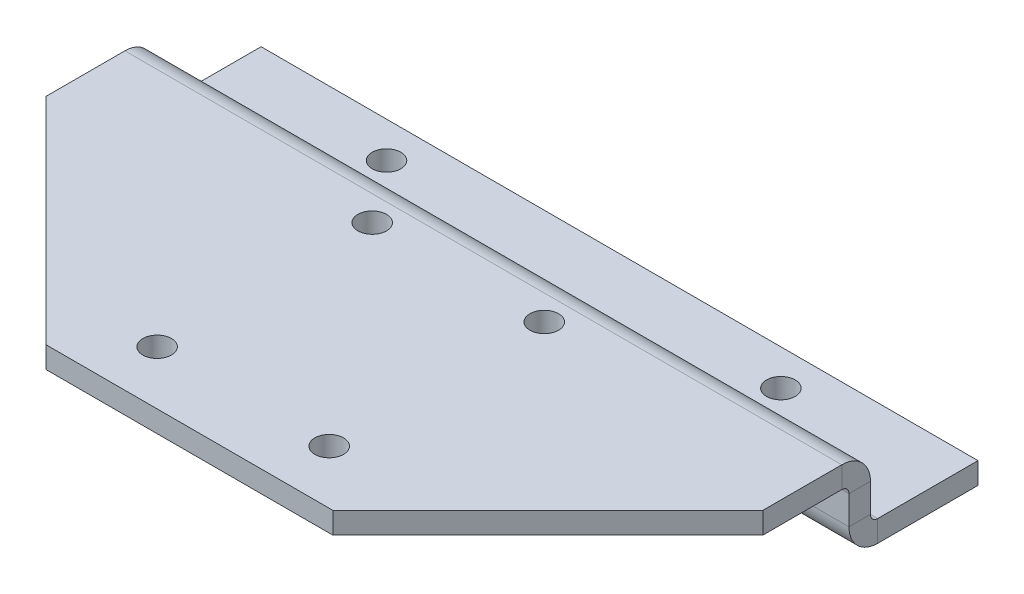
SolidWorks part; units mm, degrees
note: The reader was unsure of these and kept them because the rebuilt part matched: flange length of "Edge-Flange1", "Edge-Flange2".
material "6061 Alloy"
ref_plane "Front Plane" through (0, 0, 0) normal (0, 0, 1) x (1, 0, 0)
ref_plane "Top Plane" through (0, 0, 0) normal (0, 1, 0) x (1, 0, 0)
ref_plane "Right Plane" through (0, 0, 0) normal (1, 0, 0) x (0, 0, -1)
sketch "Sketch1" plane through (0, 0, 0) normal (0, 1, 0) x (1, 0, 0)
  line L1 (-50, 22.5) -> (50, 22.5)
  line L2 (-50, 22.5) -> (-50, -22.5)
  line L3 (-50, -22.5) -> (50, -22.5)
  line L4 (50, 22.5) -> (50, -22.5)
  line L5 (-50, 22.5) -> (50, -22.5) construction
  line L6 (-50, -22.5) -> (50, 22.5) construction
  point P0 (0, 0)
  dimension "D1" = 45
  dimension "D2" = 100
base flange "Base-Flange1" sketch "Sketch1" thickness 3 reverse thickness direction no parameters "D1"=1
edge flange "Edge-Flange1" sketch "Sketch8" flange angle 90 flange length 12 flange position material inside bend radius 1 thickness 3 relief rectangular parameters "D6"=10
sketch "Sketch8" plane through (0, -3, -22.5) normal (0, 0, -1) x (1, 0, 0)
  line L0 (50, 0) -> (-50, 0) construction
  line L1 (50, 0) -> (-50, 0)
  line L2 (-50, 0) -> (-50, 9)
  line L3 (-50, 9) -> (50, 9)
  line L4 (50, 9) -> (50, 0)
bend "EdgeBend1" bend radius 1 bend angle 90 parameters "D5"=1
edge flange "Edge-Flange2" sketch "Sketch11" flange angle 90 flange length 18 flange position material inside bend radius 1 thickness 3 relief rectangular parameters "D6"=10
sketch "Sketch11" plane through (0, -12, -22.5) normal (0, -1, 0) x (-1, 0, 0)
  line L0 (-50, 0) -> (50, 0) construction
  line L1 (-50, 0) -> (50, 0)
  line L2 (-50, 0) -> (-50, 15)
  line L3 (-50, 15) -> (50, 15)
  line L4 (50, 15) -> (50, 0)
bend "EdgeBend2" bend radius 1 bend angle 90 parameters "D5"=2
sketch "Sketch12" plane through (0, -9, 0) normal (0, 1, 0) x (1, 0, 0)
  line L0 (-50, 37.5) -> (50, 37.5) construction
  line L1 (0, 37.5) -> (0, -38.8816)
  circle A1 centre (-27.5, 32.5) radius 2
  circle A2 centre (27.5, 32.5) radius 2
  dimension "D1" = 5
  dimension "D2" = 4
  dimension "D3" = 55
extrude "Cut-Extrude1" cut sketch "Sketch12" against normal through all contours A1 | A2 normal cut yes
sketch "Sketch13" plane through (0, 0, 0) normal (0, 1, 0) x (1, 0, 0)
  line L1 (-12, 15) -> (12, 15)
  line L2 (-12, 15) -> (-12, -15)
  line L3 (-12, -15) -> (12, -15)
  line L4 (12, 15) -> (12, -15)
  line L5 (-12, 15) -> (12, -15) construction
  line L6 (-12, -15) -> (12, 15) construction
  point P0 (0, 0)
  dimension "D1" = 30
  dimension "D2" = 24
hole_wizard "Ø4.0mm Dowel Hole1" positions "3DSketch1" profile "Sketch14" hole size "Ø4.0" standard "ISO"
sketch3d "3DSketch1"
  point P0 (12, 0, -15)
  point P3 (12, 0, 15)
  point P6 (-12, 0, 15)
  point P9 (-12, 0, -15)
sketch "Sketch14" plane through (12, 0, -15) normal (1, 0, 0) x (0, 0, 1)
  line L0 (0, 0) -> (0, 13.6017)
  line L1 (0, 13.6017) -> (2, 12.4)
  line L2 (2, 12.4) -> (2, 0)
  line L5 (2, 0) -> (0, 0)
  line L10 (0, 13.6017) -> (-2, 12.4) construction
  line L11 (0, -6.35) -> (0, 107.95) construction
  dimension "Hole Dia." = 4
  dimension "Hole Depth" = 12.4
  dimension "Drill Angle" = 118
chamfer "Chamfer1" distance 30 angle 45 2 edges at (50, -1.5, 22.5) (-50, -1.5, 22.5)
sketch "Bend-Lines1" [suppressed] plane through (0, 0, 0) normal (0, 1, 0) x (1, 0, 0)
sketch "Bounding-Box1" [suppressed] plane through (0, 0, 0) normal (0, 1, 0) x (1, 0, 0)
sheet metal parameters "Sheet-Metal8" thickness 3 parameters "D1"=1
flat pattern "Flat-Pattern8" [suppressed]
sketch "Bend-Lines2" plane through (0, 0, 0) normal (0, 1, 0) x (1, 0, 0)
sketch3d "Bounding-Box2" [suppressed]
  line L0 (-50, -22.5, 0) -> (50, -22.5, 0) construction
  line L1 (-50, 22.5, 0) -> (50, 22.5, 0) construction
  line L2 (-50, -22.5, 0) -> (-50, 22.5, 0) construction
  line L3 (50, -22.5, 0) -> (50, 22.5, 0) construction
sheet metal parameters "Sheet-Metal9" thickness 3 parameters "D1"=1
flat pattern "Flat-Pattern8"
sketch "Bend-Lines2" plane through (0, 0, 0) normal (0, 1, 0) x (1, 0, 0)
  line L0 (50, 20.4635) -> (-50, 20.4635) construction
  line L1 (50, 20.4635) -> (-50, 20.4635) construction
sketch3d "Bounding-Box2" [suppressed]
  line L0 (50, -22.5, 0) -> (-50, -22.5, 0) construction
  line L1 (50, 39.427, 0) -> (-50, 39.427, 0) construction
  line L2 (50, -22.5, 0) -> (50, 39.427, 0) construction
  line L3 (-50, -22.5, 0) -> (-50, 39.427, 0) construction
bend of the flat pattern "Flatten-<EdgeBend1>1"
sheet metal parameters "Sheet-Metal10" thickness 3 parameters "D1"=1
flat pattern "Flat-Pattern8"
sketch "Bend-Lines2" plane through (0, 0, 0) normal (0, 1, 0) x (1, 0, 0)
  line L0 (50, 20.4635) -> (-50, 20.4635) construction
  line L1 (50, 20.4635) -> (-50, 20.4635) construction
  line L2 (50, 37.3905) -> (-50, 37.3905) construction
  line L3 (50, 37.3905) -> (-50, 37.3905) construction
sketch3d "Bounding-Box2" [suppressed]
  line L0 (50, -22.5, 0) -> (-50, -22.5, 0) construction
  line L1 (50, 48.354, 0) -> (-50, 48.354, 0) construction
  line L2 (50, -22.5, 0) -> (50, 48.354, 0) construction
  line L3 (-50, -22.5, 0) -> (-50, 48.354, 0) construction
bend of the flat pattern "Flatten-<EdgeBend1>1"
bend of the flat pattern "Flatten-<EdgeBend2>1"
sheet metal parameters "Sheet-Metal11" thickness 3 parameters "D1"=1
flat pattern "Flat-Pattern8"
sketch "Bend-Lines2" plane through (0, 0, 0) normal (0, 1, 0) x (1, 0, 0)
  line L0 (50, 20.4635) -> (-50, 20.4635) construction
  line L1 (50, 20.4635) -> (-50, 20.4635) construction
  line L2 (50, 37.3905) -> (-50, 37.3905) construction
  line L3 (50, 37.3905) -> (-50, 37.3905) construction
sketch3d "Bounding-Box2" [suppressed]
  line L0 (50, -22.5, 0) -> (-50, -22.5, 0) construction
  line L1 (50, 48.354, 0) -> (-50, 48.354, 0) construction
  line L2 (50, -22.5, 0) -> (50, 48.354, 0) construction
  line L3 (-50, -22.5, 0) -> (-50, 48.354, 0) construction
bend of the flat pattern "Flatten-<EdgeBend1>1"
bend of the flat pattern "Flatten-<EdgeBend2>1"
sheet metal parameters "Sheet-Metal12" thickness 3 parameters "D1"=1
flat pattern "Flat-Pattern8"
sketch "Bend-Lines2" plane through (0, 0, 0) normal (0, 1, 0) x (1, 0, 0)
  line L0 (50, 20.4635) -> (-50, 20.4635) construction
  line L1 (50, 20.4635) -> (-50, 20.4635) construction
  line L2 (50, 28.3905) -> (-50, 28.3905) construction
  line L3 (50, 28.3905) -> (-50, 28.3905) construction
sketch3d "Bounding-Box2" [suppressed]
  line L0 (50, -22.5, 0) -> (-50, -22.5, 0) construction
  line L1 (50, 44.354, 0) -> (-50, 44.354, 0) construction
  line L2 (50, -22.5, 0) -> (50, 44.354, 0) construction
  line L3 (-50, -22.5, 0) -> (-50, 44.354, 0) construction
bend of the flat pattern "Flatten-<EdgeBend1>1"
bend of the flat pattern "Flatten-<EdgeBend2>1"
